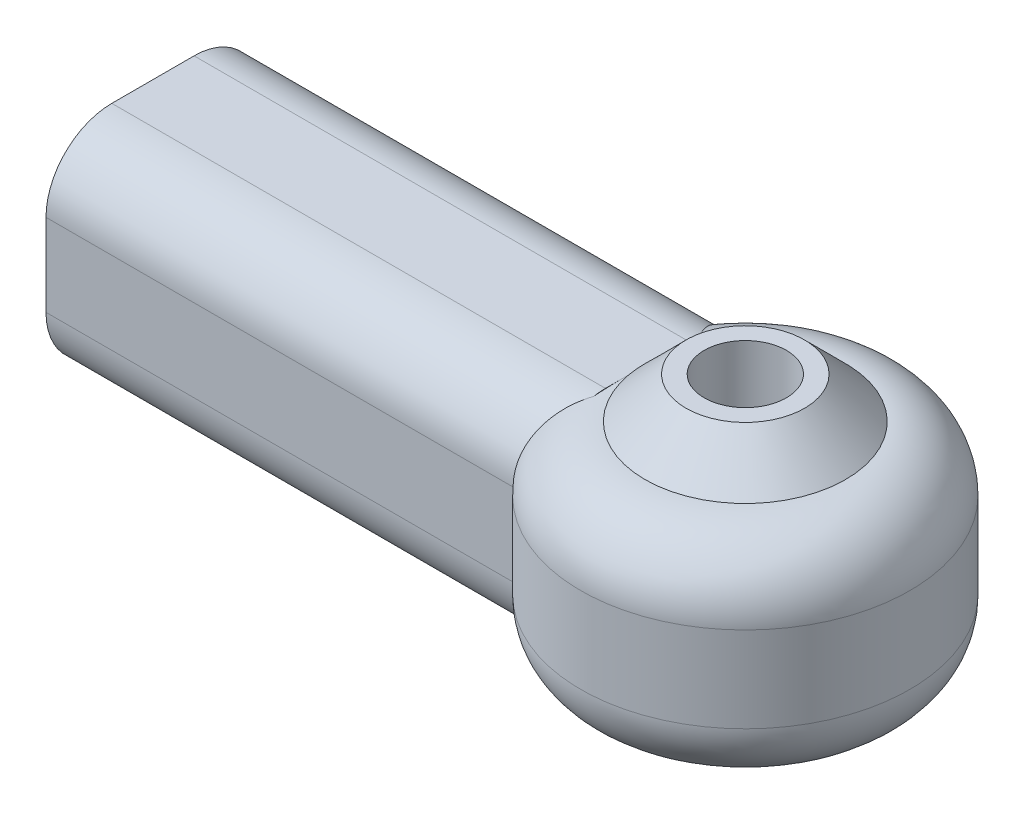
SolidWorks part; units mm, degrees
material "ABS"
ref_plane "Front Plane" through (0, 0, 0) normal (0, 0, 1) x (1, 0, 0)
ref_plane "Top Plane" through (0, 0, 0) normal (0, 1, 0) x (1, 0, 0)
ref_plane "Right Plane" through (0, 0, 0) normal (1, 0, 0) x (0, 0, -1)
sketch "Sketch1" plane through (0, 0, 0) normal (1, 0, 0) x (0, 0, -1)
  line L1 (2.5, 6.5) -> (-2.5, 6.5)
  line L2 (6.5, 2.5) -> (6.5, -2.5)
  line L3 (2.5, -6.5) -> (-2.5, -6.5)
  line L4 (-6.5, 2.5) -> (-6.5, -2.5)
  line L5 (6.5, 6.5) -> (-6.5, -6.5) construction
  line L6 (6.5, -6.5) -> (-6.5, 6.5) construction
  circle A0 centre (0, 0) radius 5
  arc A1 (-2.5, -6.5) -> (-6.5, -2.5) centre (-2.5, -2.5) cw
  arc A2 (6.5, -2.5) -> (2.5, -6.5) centre (2.5, -2.5) cw
  arc A3 (2.5, 6.5) -> (6.5, 2.5) centre (2.5, 2.5) cw
  arc A4 (-2.5, 6.5) -> (-6.5, 2.5) centre (-2.5, 2.5) ccw
  dimension "D1" = 10
  dimension "D3" = 4
  dimension "D2" = 13
extrude "Boss-Extrude1" add sketch "Sketch1" along normal blind 30 contours A0 | L1 A4 L4 A1 L3 A2 L2 A3 A0 region at (0, 5.1984, -5.1984) region at (0, 0, 0)
extrude "Cut-Extrude1" cut sketch "Sketch1<3>" along normal blind 25 contours A0 region at (0, 0, 0)
sketch "Sketch1<3>" plane through (0, 0, 0) normal (1, 0, 0) x (0, 0, -1) same geometry as "Sketch1"
chamfer "Chamfer1" distance 0.75 angle 45 1 edges at (0, 0, -5)
ref_plane "Plane1" through (36, 0, 0) normal (1, 0, 0) x (0, 0, -1)
sketch "Sketch3" plane through (36, 0, 0) normal (1, 0, 0) x (0, 0, -1)
  line L0 (0, -11.9508) -> (0, 10.4333) construction
  line L1 (-6.5, 2.5) -> (-6.5, -2.5) construction
  line L2 (2.5, -6.5) -> (-2.5, -6.5) construction
  line L3 (2.5, 6.5) -> (-2.5, 6.5) construction
  line L5 (6.5, 2.5) -> (6.5, -2.5) construction
  line L6 (-10, 2.5) -> (0, 2.5)
  line L7 (-10, 2.5) -> (-10, -2.5)
  line L8 (-10, -2.5) -> (0, -2.5)
  line L9 (0, 2.5) -> (0, -2.5)
  line L19 (2.5, -6.5) -> (-2.5, -6.5) construction
  line L20 (6.5, 2.5) -> (6.5, -2.5) construction
  line L21 (2.5, 6.5) -> (-2.5, 6.5) construction
  line L22 (-6.5, 2.5) -> (-6.5, -2.5) construction
  arc A0 (-6.5, -2.5) -> (-2.5, -6.5) centre (-2.5, -2.5) ccw construction
  arc A1 (-2.5, 6.5) -> (-6.5, 2.5) centre (-2.5, 2.5) ccw construction
  arc A3 (6.5, 2.5) -> (2.5, 6.5) centre (2.5, 2.5) ccw construction
  arc A7 (2.5, -6.5) -> (6.5, -2.5) centre (2.5, -2.5) ccw construction
  arc A21 (-6.5, -2.5) -> (-2.5, -6.5) centre (-2.5, -2.5) ccw construction
  arc A22 (2.5, -6.5) -> (6.5, -2.5) centre (2.5, -2.5) ccw construction
  arc A23 (6.5, 2.5) -> (2.5, 6.5) centre (2.5, 2.5) ccw construction
  arc A24 (-2.5, 6.5) -> (-6.5, 2.5) centre (-2.5, 2.5) ccw construction
  dimension "D1" = 5
  dimension "D2" = 10
  dimension "D3" = 4
revolve "Revolve2" add sketch "Sketch3" angle 360 about L0
sketch "Sketch4" plane through (36, 0, 0) normal (1, 0, 0) x (0, 0, -1)
  line L0 (0, -7.1029) -> (0, 9.0176) construction
  line L2 (0, 2.5) -> (-10, 2.5)
  line L3 (-6.5, 2.5) -> (6.5, 2.5)
  line L4 (2.5, 6.5) -> (-2.5, 6.5)
  line L5 (-6.5, 2.5) -> (6.5, 2.5) construction
  line L6 (2.5, 6.5) -> (-2.5, 6.5) construction
  line L7 (-10, 2.5) -> (-10, 2.6)
  line L8 (-6.1, 6.5) -> (0, 6.5)
  line L9 (0, 6.5) -> (0, 2.5)
  arc A0 (-10, 2.6) -> (-6.1, 6.5) centre (-6.1, 2.6) cw
  arc A2 (-2.5, 6.5) -> (-6.5, 2.5) centre (-2.5, 2.5) ccw
  arc A3 (6.5, 2.5) -> (2.5, 6.5) centre (2.5, 2.5) ccw
  arc A4 (-2.5, 6.5) -> (-6.5, 2.5) centre (-2.5, 2.5) ccw construction
  arc A5 (6.5, 2.5) -> (2.5, 6.5) centre (2.5, 2.5) ccw construction
  dimension "D2" = 3.9
  dimension "D1" = 0
revolve "Revolve3" add sketch "Sketch4" angle 360 about L0
ref_plane "Plane2" through (0, 0, 0) normal (0, 1, 0) x (1, 0, 0)
mirror "Mirror3" about plane through (0, 0, 0) normal (0, 1, 0) of "Revolve3"
sketch "Sketch7" plane through (0, 6.5, 0) normal (0, 1, 0) x (1, 0, 0)
  circle A0 centre (36, 0) radius 6.1
  dimension "D1" = 12.2
extrude "Boss-Extrude3" add sketch "Sketch7" along normal blind 2.5 draft 45
mirror "Mirror5" about plane through (0, 0, 0) normal (0, 1, 0) of "Boss-Extrude3"
sketch "Sketch8" plane through (0, 9, 0) normal (0, 1, 0) x (1, 0, 0)
  circle A0 centre (36, 0) radius 2.5
  dimension "D1" = 5
extrude "Cut-Extrude3" cut sketch "Sketch8" against normal blind 200 and the other way through all
